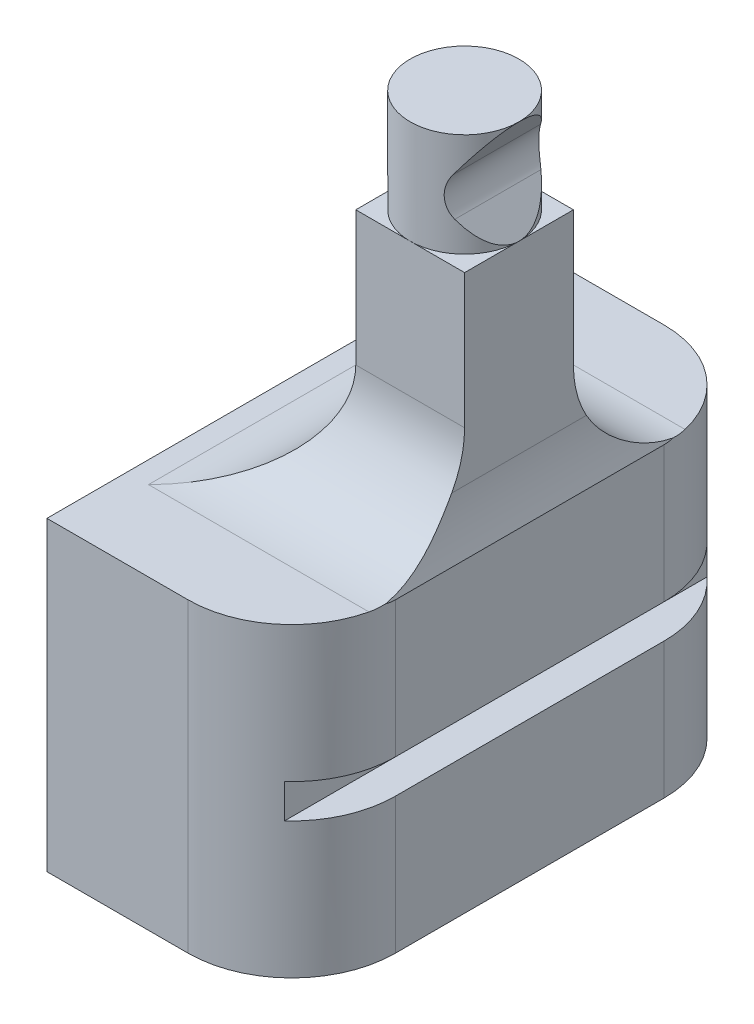
SolidWorks part; units mm, degrees
ref_plane "Front Plane" through (0, 0, 0) normal (0, 0, 1) x (1, 0, 0)
ref_plane "Top Plane" through (0, 0, 0) normal (0, 1, 0) x (1, 0, 0)
ref_plane "Right Plane" through (0, 0, 0) normal (1, 0, 0) x (0, 0, -1)
sketch "Sketch1" plane through (0, 0, 0) normal (0, 1, 0) x (1, 0, 0)
  line L1 (5.6786, 14.1116) -> (23.6786, 14.1116)
  line L2 (5.6786, 14.1116) -> (5.6786, -20.8884)
  line L3 (5.6786, -20.8884) -> (23.6786, -20.8884)
  line L4 (23.6786, 14.1116) -> (23.6786, -20.8884)
  line L5 (5.6786, 14.1116) -> (23.6786, 14.1116)
  line L6 (5.6786, 14.1116) -> (5.6786, 11.6116)
  line L7 (5.6786, 11.6116) -> (23.6786, 11.6116)
  line L8 (23.6786, 14.1116) -> (23.6786, 11.6116)
  line L9 (5.6786, -20.8884) -> (23.6786, -20.8884)
  line L10 (5.6786, -20.8884) -> (5.6786, -18.3884)
  line L11 (5.6786, -18.3884) -> (23.6786, -18.3884)
  line L12 (23.6786, -20.8884) -> (23.6786, -18.3884)
  line L13 (23.6786, 11.6116) -> (21.1786, 11.6116)
  line L14 (23.6786, 11.6116) -> (23.6786, -18.3884)
  line L15 (23.6786, -18.3884) -> (21.1786, -18.3884)
  line L16 (21.1786, 11.6116) -> (21.1786, -18.3884)
  dimension "D1" = 35
  dimension "D2" = 18
  dimension "D3" = 2.5
  dimension "D4" = 2.5
  dimension "D5" = 2.5
extrude "Boss-Extrude1" add sketch "Sketch1" along normal blind 2.5 contours L16 L7 L2 L11 | L11 L2 L3 L4 | L7 L16 L11 L4 | L2 L7 L4 L1 region at (14.6786, 0, -12.8616) region at (13.4286, 0, 3.3884) region at (22.4286, 0, 3.3884) region at (14.6786, 0, 19.6384)
sketch "Sketch2" plane through (0, 2.5, 0) normal (0, 1, 0) x (1, 0, 0)
  line L0 (23.6786, 14.1116) -> (23.6786, -20.8884) construction
  line L1 (5.6786, 14.1116) -> (23.6786, 14.1116)
  line L2 (5.6786, 14.1116) -> (5.6786, 11.6116)
  line L3 (5.6786, 11.6116) -> (23.6786, 11.6116)
  line L4 (23.6786, 14.1116) -> (23.6786, 11.6116)
  line L6 (5.6786, -20.8884) -> (23.6786, -20.8884)
  line L7 (5.6786, -20.8884) -> (5.6786, -18.3884)
  line L8 (5.6786, -18.3884) -> (23.6786, -18.3884)
  line L9 (23.6786, -20.8884) -> (23.6786, -18.3884)
  line L10 (23.6786, 11.6116) -> (21.1786, 11.6116)
  line L11 (23.6786, 11.6116) -> (23.6786, -18.3884)
  line L12 (23.6786, -18.3884) -> (21.1786, -18.3884)
  line L13 (21.1786, 11.6116) -> (21.1786, -18.3884)
  line M7 (23.6786, -20.8884) -> (23.6786, 14.1116)
  line M8 (23.6786, 14.1116) -> (5.6786, 14.1116)
  line M9 (5.6786, 14.1116) -> (5.6786, -20.8884)
  line M10 (5.6786, -20.8884) -> (23.6786, -20.8884)
  dimension "D1" = 2.5
  dimension "D2" = 2.5
  dimension "D3" = 2.5
extrude "Boss-Extrude2" add sketch "Sketch2" along normal blind 20 contours L3 M9 M7 M8 | L3 L13 L8 M7 | L8 M9 M10 M7 region at (14.6786, 2.5, -12.8616) region at (22.4286, 2.5, 3.3884) region at (14.6786, 2.5, 19.6384)
sketch "Sketch3" plane through (0, 2.5, 0) normal (0, 1, 0) x (1, 0, 0)
  line L0 (5.6786, 11.6116) -> (5.6786, -18.3884) construction
  circle A0 centre (5.6786, -3.3884) radius 7.5
  dimension "D1" = 15
extrude "Cut-Extrude1" cut sketch "Sketch3" against normal blind 7.58
sketch "Sketch4" plane through (21.1786, 0, 0) normal (-1, 0, 0) x (0, 0, 1)
  line L0 (18.3884, 22.5) -> (18.3884, 2.5) construction
  line L1 (-11.6116, 22.5) -> (18.3884, 22.5)
  line L2 (-11.6116, 22.5) -> (-11.6116, 20)
  line L3 (-11.6116, 20) -> (18.3884, 20)
  line L4 (18.3884, 22.5) -> (18.3884, 20)
  dimension "D1" = 2.5
extrude "Boss-Extrude3" add sketch "Sketch4" along normal up to surface (15.5 mm away) up to face at (5.6786, 8.3333, 16.7217)
fillet "Fillet3" radius 7.62 2 edges at (23.6786, 11.25, -14.1116) (23.6786, 11.25, 20.8884)
fillet "Fillet4" radius 7.62 2 edges at (21.1786, 11.25, -11.6116) (21.1786, 11.25, 18.3884)
fillet "Fillet5" radius 2.54 1 edges at (13.1786, 2.5, 3.3884)
sketch "Sketch10" plane through (0, 22.5, 0) normal (0, 1, 0) x (1, 0, 0)
  line L0 (8.3814, -2.4001) -> (32.934, -4.7098) construction
  line L1 (5.6786, 14.1116) -> (5.6786, -20.8884) construction
  line L2 (14.8866, 0.6116) -> (22.8866, 0.6116)
  line L4 (14.8866, 0.6116) -> (14.8866, -7.3884)
  line L5 (14.8866, -7.3884) -> (22.8866, -7.3884)
  line L6 (22.8866, 0.6116) -> (22.8866, -7.3884)
  line L7 (14.8866, 0.6116) -> (22.8866, -7.3884) construction
  line L8 (14.8866, -7.3884) -> (22.8866, 0.6116) construction
  line L9 (5.6786, -3.3884) -> (23.6786, -3.3884) construction
  line L10 (23.6786, -13.2684) -> (23.6786, 6.4916) construction
  point P3 (18.8866, -3.3884)
  dimension "D1" = 8
  dimension "D2" = 8
  dimension "D3" = 13.208
extrude "Boss-Extrude6" add sketch "Sketch10" along normal blind 17.5
sketch "Sketch11" plane through (0, 40, 0) normal (0, 1, 0) x (1, 0, 0)
  line L0 (12.1749, -3.3884) -> (22.1749, -3.3884) construction
  line L1 (5.6786, 14.1116) -> (5.6786, -20.8884) construction
  circle A1 centre (18.8866, -3.3884) radius 4
  dimension "D1" = 8
  dimension "D2" = 13.208
extrude "Boss-Extrude7" add sketch "Sketch11" along normal blind 7.6
sketch "Sketch12" plane through (0, 0, 0) normal (0, 0, 1) x (1, 0, 0)
  line L0 (22.8866, 40) -> (20.3466, 43.5857)
  line L1 (20.3466, 43.5857) -> (22.8866, 47.6)
  line L2 (22.8866, 47.6) -> (22.8866, 40)
  dimension "D1" = 2.54
extrude "Cut-Extrude4" cut sketch "Sketch12" against normal blind 7.6 and the other way blind 7.6
fillet "Fillet11" radius 7.62 3 edges at (18.8866, 22.5, -0.6116) (14.8866, 22.5, 3.3884) (18.8866, 22.5, 7.3884)
fillet "Fillet12" radius 10.16 1 edges at (22.8866, 22.5, 3.3884)
fillet "Fillet13" radius 2.54 1 edges at (20.3466, 43.5857, 3.3884)
sketch "Sketch13" plane through (23.6786, 0, 0) normal (1, 0, 0) x (0, 0, -1)
  line L0 (-13.2684, 11.25) -> (6.4916, 11.25) construction
  line L1 (-13.2684, 22.5) -> (-13.2684, 0) construction
  line L2 (6.4916, 0) -> (6.4916, 22.5) construction
  line L4 (-31.2318, 12.5) -> (24.4551, 12.5)
  line L5 (-31.2318, 12.5) -> (-31.2318, 10)
  line L6 (-31.2318, 10) -> (24.4551, 10)
  line L7 (24.4551, 12.5) -> (24.4551, 10)
  line L8 (-31.2318, 12.5) -> (24.4551, 10) construction
  line L9 (-31.2318, 10) -> (24.4551, 12.5) construction
  point P7 (-3.3884, 11.25)
  dimension "D1" = 2.5
extrude "Cut-Extrude5" cut sketch "Sketch13" against normal blind 2.5
